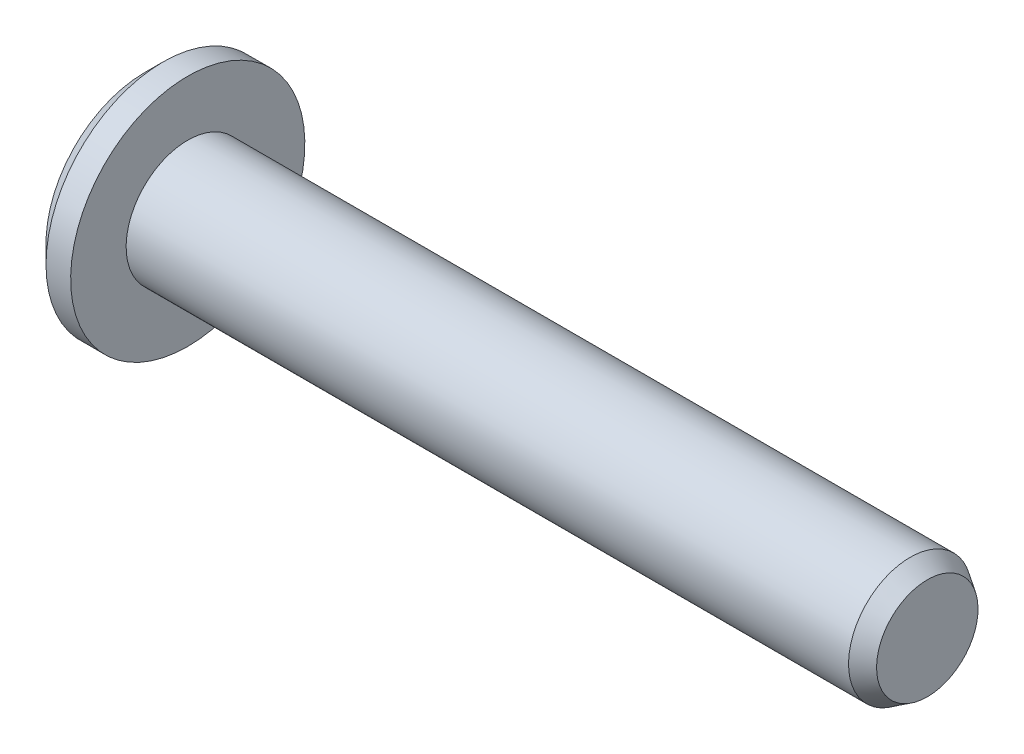
SolidWorks part; units mm, degrees
ref_plane "Front Plane" through (0, 0, 0) normal (0, 0, 1) x (1, 0, 0)
ref_plane "Top Plane" through (0, 0, 0) normal (0, 1, 0) x (1, 0, 0)
ref_plane "Right Plane" through (0, 0, 0) normal (1, 0, 0) x (0, 0, -1)
ref_plane "Plane1" through (5, 0, 0) normal (1, 0, 0) x (0, 0, -1)
sketch "Sketch1" plane through (0, 0, 0) normal (0, 0, 1) x (1, 0, 0)
  line L0 (31.75, 0) -> (31.75, 2.0572)
  line L1 (31.055, 2.5) -> (1.75, 2.5)
  line L2 (1.75, 2.5) -> (1.75, 4.75)
  line L3 (1.75, 4.75) -> (0, 4.75)
  line L4 (0, 0) -> (101.6, 0) construction
  line L7 (31.75, 0) -> (0, 0)
  line L9 (0, 4.75) -> (0, 0)
  line L10 (31.75, 2.0572) -> (31.055, 2.5)
  line L14 (0, 4.75) -> (0, 0) construction
  dimension "D1" = 30
  dimension "D2" = 2.5
  dimension "D3" = 1.75
  dimension "D4" = 122.5
  dimension "D5" = 2.0572
  dimension "D6" = 2.25
revolve "Revolve1" add sketch "Sketch1" angle 360 about L4
sketch "Sketch2" plane through (1.75, 0, 0) normal (1, 0, 0) x (0, 0, -1)
  circle A0 centre (0, 0) radius 2.55
  dimension "D1" = 5.1
curve "Helix/Spiral1" pitch 0.8 height 64 turns 80
sketch "Sketch4" plane through (0, 0, 0) normal (0, 0, 1) x (1, 0, 0)
  line L0 (26.9044, 2.5) -> (26.1244, 2.5)
  line L1 (26.9044, 2.5) -> (26.5079, 2.1165)
  line L2 (26.5079, 2.1165) -> (26.1244, 2.5)
  dimension "D1" = 0.78
  dimension "D2" = 45
  dimension "D3" = 2.5
sweep "Cut-Sweep2" [suppressed] cut profiles "Sketch4" path "Helix/Spiral1"
sketch "Sketch5" plane through (0, 0, 0) normal (-1, 0, 0) x (0, 0, 1)
  line L1 (1.5, -0.866) -> (1.5, 0.866)
  line L2 (1.5, 0.866) -> (0, 1.7321)
  line L3 (0, 1.7321) -> (-1.5, 0.866)
  line L4 (-1.5, 0.866) -> (-1.5, -0.866)
  line L5 (-1.5, -0.866) -> (0, -1.7321)
  line L6 (0, -1.7321) -> (1.5, -0.866)
  circle A0 centre (0, 0) radius 1.5 construction
  dimension "D1" = 3
extrude "Cut-Extrude1" cut sketch "Sketch5" against normal blind 1
chamfer "Chamfer1" distance 0.75 angle 45 1 edges at (0, -4.75, 0)
